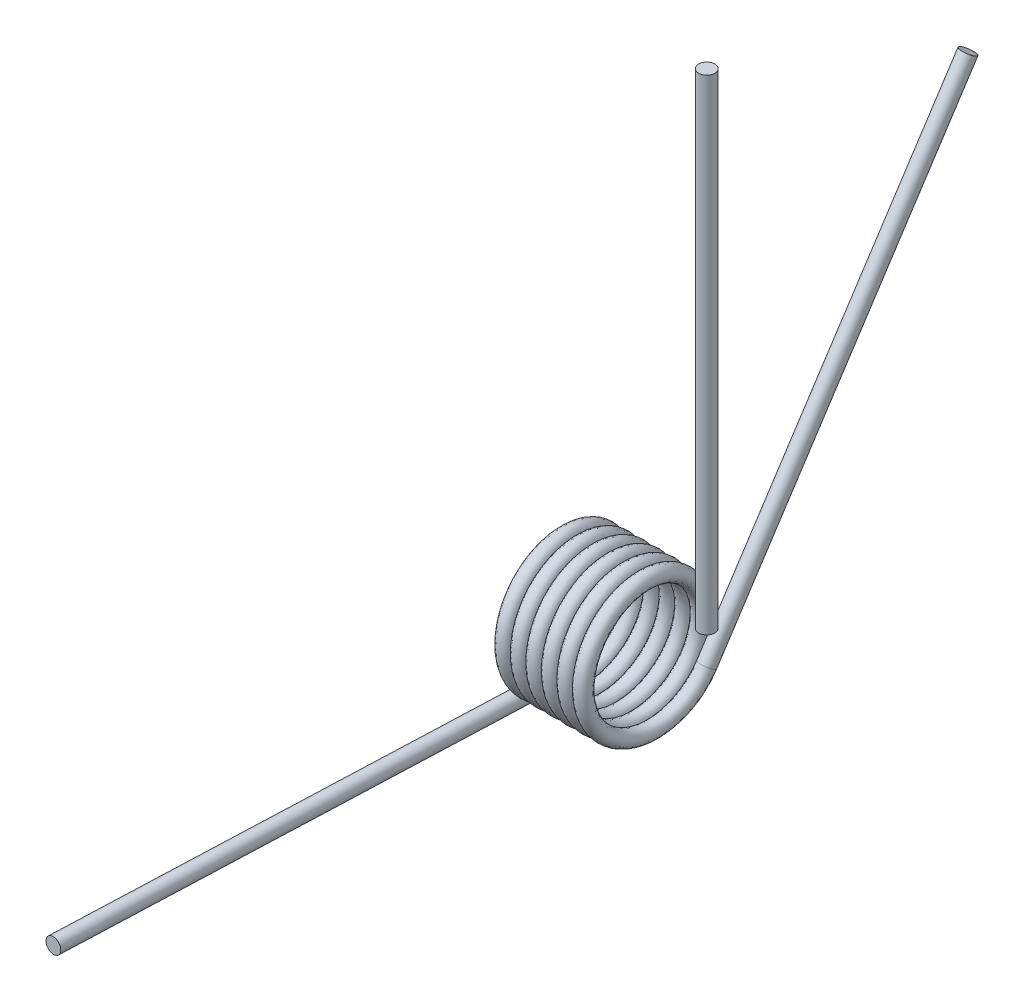
SolidWorks part; units mm, degrees
ref_plane "Front" through (0, 0, 0) normal (0, 0, 1) x (1, 0, 0)
ref_plane "Top" through (0, 0, 0) normal (0, 1, 0) x (1, 0, 0)
ref_plane "Right" through (0, 0, 0) normal (1, 0, 0) x (0, 0, -1)
sketch "Sketch1" plane through (0, 0, 0) normal (1, 0, 0) x (0, 0, -1)
  line L0 (0, -8.6487) -> (0, -11.0617) construction
  line L1 (9.5797, -5.5309) -> (47.6797, 60.4603) construction
  line L2 (0, -11.0617) -> (-76.2, -11.0617) construction
  line L3 (0, 0) -> (11.0617, 0) construction
  line L4 (0, 0) -> (9.5797, -5.5309) construction
  line L5 (-76.2, -11.0617) -> (-76.2, -8.6487) construction
  line L6 (-76.2, -8.6487) -> (0, -8.6487) construction
  line L7 (47.6797, 60.4603) -> (45.59, 61.6668) construction
  line L8 (45.59, 61.6668) -> (7.49, -4.3244) construction
  circle A0 centre (0, 0) radius 11.0617 construction
  circle A1 centre (0, 0) radius 7.9375 construction
  circle A2 centre (0, 0) radius 9.8552 construction
  point P7 (0, -9.8552)
  point P10 (0, 11.0617)
  dimension "OD" = 22.1234
  dimension "For Shaft Diameter" = 15.875
  dimension "Wire Diameter" = 2.413
  dimension "Leg Length" = 76.2
  dimension "Deflection Angle" = 120
sketch "Sketch2" plane through (0, 0, 0) normal (1, 0, 0) x (0, 0, -1)
  circle A0 centre (0, 0) radius 9.8552 construction
  circle A2 centre (0, 0) radius 9.8552
curve "Helix/Spiral1" pitch 2.4384 height 15.0368 radius 9.8552 centre (0, 0, 0) axis (1, 0, 0) start towards (0, 0, -1)
ref_plane "Plane1" through (0, -9.8552, 0) normal (0.0393, 0, -0.9992) x (0.999, -0.0232, 0.0393)
sketch "Sketch3" plane through (0, -9.8552, 0) normal (0.0393, 0, -0.9992) x (0.999, -0.0232, 0.0393)
  circle A0 centre (0, 0) radius 1.2065
  dimension "D1" = 2.413
sweep "Sweep1" add profiles "Sketch3" path "Helix/Spiral1"
sketch "Sketch4" plane through (0, 0, 0) normal (-0.0393, 0, 0.9992) x (-0.999, 0.0232, -0.0393)
  circle A1 centre (-0.229, 9.8525) radius 1.2065
  circle A2 centre (-0.229, 9.8525) radius 1.2065
  dimension "D1" = 0
extrude "Extrude1" add sketch "Sketch4" along normal blind 76.2
sketch "Sketch5" plane through (0.0233, 0.512, -0.2956) normal (0.0393, 0.8654, -0.4996) x (0.9982, -0.0569, -0.02)
  circle A1 centre (15.4605, 9.1571) radius 1.2065
  circle A2 centre (15.4605, 9.1571) radius 1.2065
  dimension "D1" = 0
extrude "Extrude2" add sketch "Sketch5" along normal blind 76.2
sketch "Sketch6" plane through (0, 0, 0) normal (1, 0, 0) x (0, 0, -1)
  circle A2 centre (0, 0) radius 8.6487 construction
sketch "Sketch7" plane through (0, 0, 0) normal (0, 1, 0) x (1, 0, 0)
  circle A0 centre (15.0368, 8.5349) radius 1.27
  ellipse E0 centre (15.0368, 8.5349) end of major axis (13.834, 8.6296) minor radius 1.0441 construction
  dimension "D1" = 2.54
extrude "Boss-Extrude1" add sketch "Sketch7" along normal blind 76.2
sketch "Sketch8" plane through (0, 0, 0) normal (1, 0, 0) x (0, 0, -1)
  circle A0 centre (0, 0) radius 17.4684
equation "\"D4@Helix/Spiral1\" = \"Wire Diameter@Sketch1\" + .001"
equation "\"D1@Sketch3\"=\"Wire Diameter@Sketch1\""
equation "\"D1@Extrude2\"=\"Leg Length@Sketch1\""
equation "\"Leg Length@Extrude1\"=\"Leg Length@Sketch1\""
